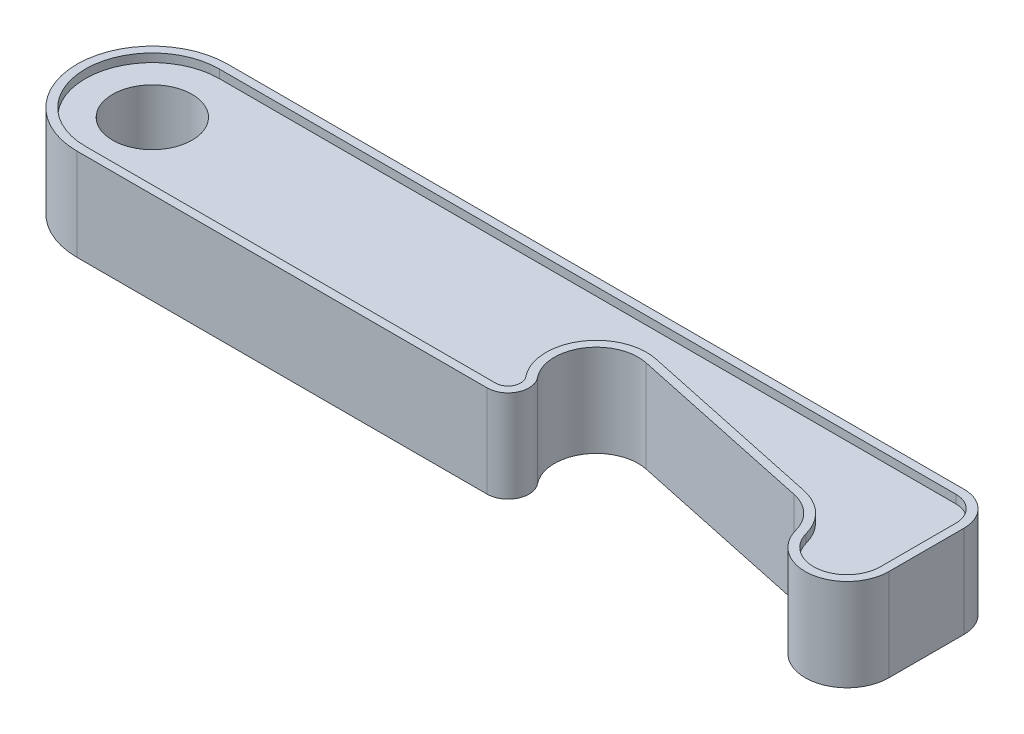
SolidWorks part; units mm, degrees
material "AISI 1020"
ref_plane "Front Plane" through (0, 0, 0) normal (0, 0, 1) x (1, 0, 0)
ref_plane "Top Plane" through (0, 0, 0) normal (0, 1, 0) x (1, 0, 0)
ref_plane "Right Plane" through (0, 0, 0) normal (1, 0, 0) x (0, 0, -1)
sketch "Sketch2" plane through (0, 0, 0) normal (0, 1, 0) x (1, 0, 0)
  line L4 (0, 9) -> (88, 9)
  line L8 (49, -9) -> (0, -9)
  line L10 (55.8798, 3.0963) -> (78.3772, -1.6857)
  line L11 (92, -4) -> (92, 5)
  line L12 (0, 8) -> (88, 8)
  line L13 (91, -4) -> (91, 5)
  line L14 (56.0877, 4.0744) -> (78.5851, -0.7076)
  line L15 (49, -8) -> (0, -8)
  line L16 (0, 8) -> (91, 8) construction
  line L17 (91, -4) -> (91, 8) construction
  line L18 (92, -4) -> (92, 9) construction
  line L19 (0, 9) -> (92, 9) construction
  circle A11 centre (0, 0) radius 4.75
  arc A17 (0, -9) -> (0, 9) centre (0, 0) cw
  arc A18 (49, -9) -> (50.9467, -4.9315) centre (49, -6.5) ccw
  arc A19 (50.9467, -4.9315) -> (55.8798, 3.0963) centre (54.8402, -1.7945) cw
  arc A20 (78.3772, -1.6857) -> (82.1688, -5.2882) centre (77.3376, -6.5764) cw
  arc A21 (82.1688, -5.2882) -> (92, -4) centre (87, -4) ccw
  arc A23 (83.135, -5.0306) -> (91, -4) centre (87, -4) ccw
  arc A24 (78.5851, -0.7076) -> (83.135, -5.0306) centre (77.3376, -6.5764) cw
  arc A25 (50.168, -5.5589) -> (56.0877, 4.0744) centre (54.8402, -1.7945) cw
  arc A26 (49, -8) -> (50.168, -5.5589) centre (49, -6.5) ccw
  arc A27 (0, -8) -> (0, 8) centre (0, 0) cw
  arc A28 (88, 8) -> (91, 5) centre (88, 5) cw
  arc A29 (92, 5) -> (88, 9) centre (88, 5) ccw
  point P17 (-9, 0)
  dimension "D2" = 9.5
  dimension "D3" = 2.5
  dimension "D6" = 5
  dimension "D10" = 4
  dimension "D11" = 5
  dimension "D4" = 18
  dimension "D1" = 38
  dimension "D5" = 12
  dimension "D8" = 22.4974
extrude "Boss-Extrude1" add sketch "Sketch2" along normal mid plane 9 contours A27 L15 A26 A25 L14 A24 A23 L13 L12 A11 | A20 A21 L11 L4 A17 L8 A18 A19 L10 L15 A27 L12 L13 A23 A24 L14 A25 A26 region at (44, 0, -8.8974) region at (38.4871, 0, -0.8569)
extrude "Boss-Extrude2" add sketch "Sketch2<3>" along normal mid plane 11 contours A20 A21 L11 L4 A17 L8 A18 A19 L10 L15 A27 L12 L13 A23 A24 L14 A25 A26 region at (44, 0, -8.8974)
sketch "Sketch2<3>" plane through (0, 0, 0) normal (0, 1, 0) x (1, 0, 0) same geometry as "Sketch2"
equation "\"A\"= 101mm"
equation "\"B\"= 11"
equation "\"D7@Sketch2\"=\"A\""
equation "\"D1@Boss-Extrude2\"=\"B\""
equation "\"C\"= 1"
equation "\"D1@Boss-Extrude1\"=\"B\"-\"C\"*2"
equation "\"D9@Sketch2\"=\"C\""
